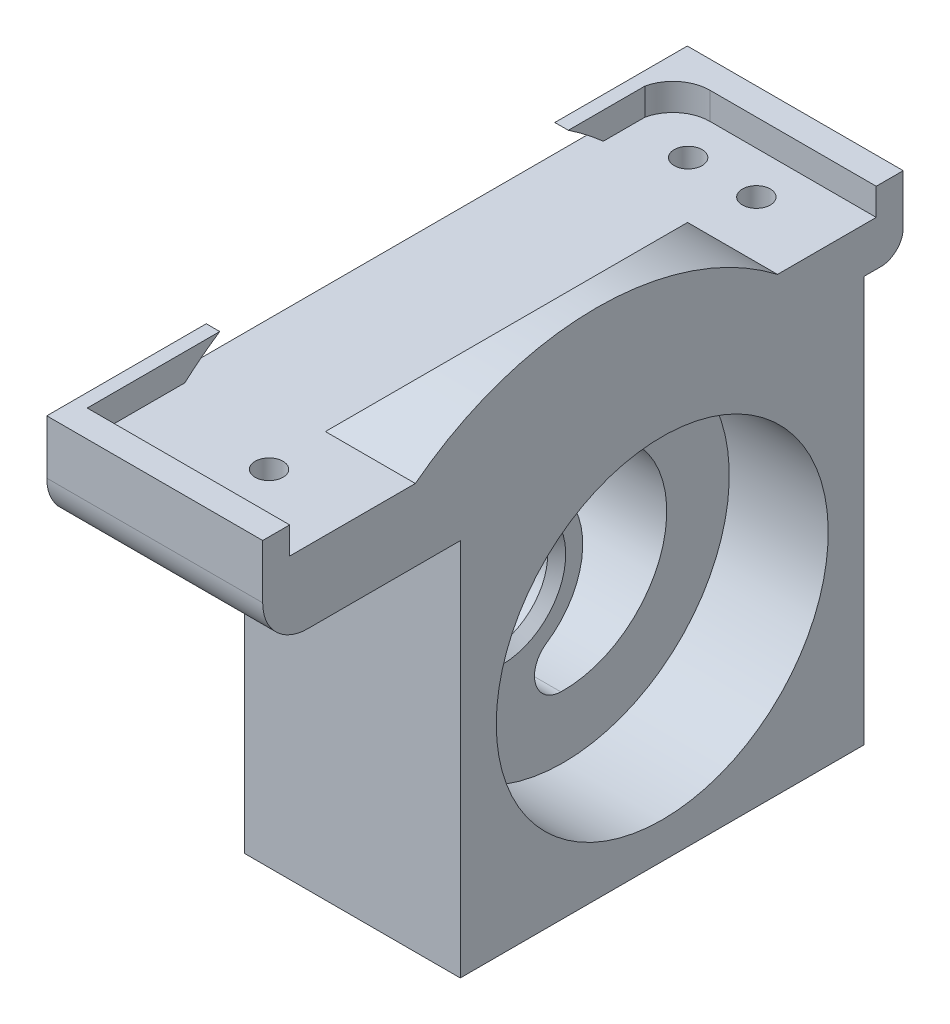
SolidWorks part; units mm, degrees
note: The reader was unsure of these and kept them because the rebuilt part matched: shared geometry of "Sketch1<3>", "Sketch1<4>", "Sketch3<3>", "Sketch3<4>", "Sketch3<5>".
ref_plane "Front Plane" through (0, 0, 0) normal (0, 0, 1) x (1, 0, 0)
ref_plane "Top Plane" through (0, 0, 0) normal (0, 1, 0) x (1, 0, 0)
ref_plane "Right Plane" through (0, 0, 0) normal (1, 0, 0) x (0, 0, -1)
sketch "Sketch1" plane through (-50.6502, 0, 0) normal (-1, 0, 0) x (0, 0, 1)
  line L1 (19.0917, -47.1626) -> (63.9917, -47.1626)
  line L2 (63.9917, -47.1626) -> (63.9917, -5.0626)
  line L3 (63.9917, -5.0626) -> (80.9548, -5.0626)
  line L4 (85.9548, -0.0626) -> (85.9548, 5.9374)
  line L5 (85.9548, 5.9374) -> (82.9548, 5.9374)
  line L6 (82.9548, 5.9374) -> (82.9548, 2.9374)
  line L7 (82.9548, 2.9374) -> (17.7548, 2.9374)
  line L8 (17.7548, 2.9374) -> (17.7548, 5.9374)
  line L9 (17.7548, 5.9374) -> (14.7548, 5.9374)
  line L10 (14.7548, 5.9374) -> (14.7548, 0.4374)
  line L11 (14.7548, 0.4374) -> (14.7548, 5.9374) construction
  line L13 (17.2548, -2.0626) -> (19.0917, -2.0626)
  line L14 (19.0917, -2.0626) -> (19.0917, -47.1626)
  line L15 (19.0917, -2.0626) -> (17.2548, -2.0626) construction
  line L16 (19.0917, -24.7126) -> (19.0917, -2.0626) construction
  line L17 (63.9917, -47.1626) -> (19.0917, -47.1626) construction
  line L18 (63.9917, -24.7126) -> (63.9917, -47.1626) construction
  line L19 (14.7548, 5.9374) -> (17.7548, 5.9374) construction
  line L20 (17.7548, 5.9374) -> (17.7548, 2.9374) construction
  line L21 (17.7548, 2.9374) -> (82.9548, 2.9374) construction
  line L22 (82.9548, 2.9374) -> (82.9548, 5.9374) construction
  line L23 (82.9548, 5.9374) -> (85.9548, 5.9374) construction
  line L24 (85.9548, 5.9374) -> (85.9548, -0.0626) construction
  line L25 (80.9548, -5.0626) -> (63.9917, -5.0626) construction
  circle A0 centre (48.3792, -23.2131) radius 6.11
  circle A1 centre (48.3792, -23.2131) radius 3.075
  circle A2 centre (48.3792, -23.2131) radius 6.11 construction
  circle A3 centre (48.3792, -23.2131) radius 3.075 construction
  circle A4 centre (41.5417, -24.7126) radius 18.45
  circle A5 centre (41.5417, -24.7126) radius 18.45 construction
  circle A6 centre (41.5417, -24.7126) radius 22.45
  circle A7 centre (41.5417, -24.7126) radius 22.45 construction
  arc A8 (80.9548, -5.0626) -> (85.9548, -0.0626) centre (80.9548, -0.0626) ccw
  arc A9 (14.7548, 0.4374) -> (17.2548, -2.0626) centre (17.2548, 0.4374) ccw
  arc A10 (14.7548, 0.4374) -> (17.2548, -2.0626) centre (17.2548, 0.4374) ccw construction
  arc A11 (80.9548, -5.0626) -> (85.9548, -0.0626) centre (80.9548, -0.0626) ccw construction
  circle M20 centre (48.3792, -23.2131) radius 5.25
extrude "Boss-Extrude1" add sketch "Sketch1" along normal up to surface (5.5 mm away) contours A1 M20 | A0 M20 | A4 A0 | A6 A4 | A6 L14 L1 | A6 L1 L2 | L10 A9 L13 L14 A6 L2 L3 A8 L4 L5 L6 L7 L8 L9
extrude "Boss-Extrude2" add sketch "Sketch1<3>" against normal up to surface (6 mm away) contours A4 A0 | A6 A4 | A6 L14 L1 | A6 L1 L2 | L10 A9 L13 L14 A6 L2 L3 A8 L4 L5 L6 L7 L8 L9
sketch "Sketch1<3>" plane through (-50.6502, 0, 0) normal (-1, 0, 0) x (0, 0, 1) same geometry as "Sketch1"
extrude "Boss-Extrude3" add sketch "Sketch1<4>" against normal up to surface (11 mm away) from surface at -6 contours A6 L14 L1 | A6 L1 L2 | A6 A4 | L10 A9 L13 L14 A6 L2 L3 A8 L4 L5 L6 L7 L8 L9 starting at face at (-44.6502, -5.7236, 47.6952)
sketch "Sketch1<4>" plane through (-50.6502, 0, 0) normal (-1, 0, 0) x (0, 0, 1) same geometry as "Sketch1"
sketch "Sketch2" plane through (-33.6502, 0, 0) normal (1, 0, 0) x (0, 0, -1)
  line L0 (-17.7548, 2.9374) -> (-82.9548, 2.9374) construction
  line L1 (-28.7263, 2.9374) -> (-68.9833, 2.9374)
  arc A0 (-28.7263, 2.9374) -> (-68.9833, 2.9374) centre (-48.8548, -23.2131) ccw
  arc A1 (-28.7263, 2.9374) -> (-68.9833, 2.9374) centre (-48.8548, -23.2131) ccw construction
  line M7 (-17.7548, 2.9374) -> (-82.9548, 2.9374)
extrude "Boss-Extrude4" add sketch "Sketch2" against normal blind 10 contours A0 M7
draft "Draft1" type of draft neutral plane draft angle 45 faces to draft 1 face at (-43.6502, 6.3621, 48.8548) neutral plane through (-144.9705, 2.9374, 0) neutral plane normal (0, 1, 0) parameters "D1"=45
sketch "Sketch3" plane through (0, 2.9374, 0) normal (0, 1, 0) x (1, 0, 0)
  line L0 (-56.1502, -17.7548) -> (-33.6502, -17.7548) construction
  line L1 (-56.1502, -82.9548) -> (-56.1502, -17.7548) construction
  line L2 (-56.1502, -17.7548) -> (-33.6502, -17.7548) construction
  line L3 (85.3271, -19.0917) -> (85.3271, -24.1003) construction
  line L4 (-42.2775, -25.7457) -> (-39.4275, -24.1003)
  line L5 (-39.4275, -24.1003) -> (-39.4275, -20.8094)
  line L6 (-39.4275, -20.8094) -> (-42.2775, -19.1639)
  line L7 (-42.2775, -19.1639) -> (-45.1275, -20.8094)
  line L8 (-45.1275, -20.8094) -> (-45.1275, -24.1003)
  line L9 (-45.1275, -24.1003) -> (-42.2775, -25.7457)
  line L10 (-49.8593, -25.7457) -> (-47.0093, -24.1003)
  line L11 (-47.0093, -24.1003) -> (-47.0093, -20.8094)
  line L12 (-47.0093, -20.8094) -> (-49.8593, -19.1639)
  line L13 (-49.8593, -19.1639) -> (-52.7093, -20.8094)
  line L14 (-52.7093, -20.8094) -> (-52.7093, -24.1003)
  line L15 (-52.7093, -24.1003) -> (-49.8593, -25.7457)
  line L16 (-39.8593, -75.7484) -> (-41.5048, -72.8984)
  line L17 (-41.5048, -72.8984) -> (-44.7957, -72.8984)
  line L18 (-44.7957, -72.8984) -> (-46.4411, -75.7484)
  line L19 (-46.4411, -75.7484) -> (-44.7957, -78.5984)
  line L20 (-44.7957, -78.5984) -> (-41.5048, -78.5984)
  line L21 (-41.5048, -78.5984) -> (-39.8593, -75.7484)
  line L23 (90.6952, -72.8984) -> (87.4043, -72.8984) construction
  line L24 (85.3271, -24.1003) -> (88.1771, -25.7457) construction
  line L25 (-52.7093, -20.8094) -> (-52.7093, -19.0917)
  line L26 (-52.7093, -19.0917) -> (-47.0093, -19.0917)
  line L27 (-47.0093, -19.0917) -> (-47.0093, -20.8094)
  line L28 (-45.1275, -20.8094) -> (-45.1275, -19.0917)
  line L29 (-45.1275, -19.0917) -> (-39.4275, -19.0917)
  line L30 (-39.4275, -19.0917) -> (-39.4275, -20.8094)
  line L31 (-56.1502, -19.0917) -> (-33.6502, -19.0917) construction
  arc A0 (-52.1502, -17.7548) -> (-56.1502, -20.9548) centre (-52.1502, -21.8548) ccw
  arc A1 (-52.1502, -17.8548) -> (-56.1502, -21.8548) centre (-52.1502, -21.8548) ccw construction
  circle A2 centre (-49.8593, -22.4548) radius 1.55
  circle A3 centre (-42.2775, -22.4548) radius 1.55
  circle A4 centre (-49.8593, -22.4548) radius 1.55 construction
  circle A5 centre (-42.2775, -22.4548) radius 1.55 construction
  circle A6 centre (-43.1502, -75.7484) radius 1.55
  circle A7 centre (-43.1502, -75.7484) radius 1.55 construction
  circle A8 centre (-42.2775, -22.4548) radius 2.85 construction
  circle A9 centre (-49.8593, -22.4548) radius 2.85 construction
  circle A10 centre (-43.1502, -75.7484) radius 2.85 construction
  line M15 (-33.6502, -17.7548) -> (-56.1502, -17.7548)
  line M16 (-56.1502, -17.7548) -> (-56.1502, -82.9548)
extrude "Boss-Extrude5" add sketch "Sketch3" along normal up to surface (3 mm away) contours A0 M15 M16 up to face at (-44.9002, 5.9374, 16.2548)
sketch "Sketch4" plane through (-56.1502, 0, 0) normal (-1, 0, 0) x (0, 0, 1)
  line L0 (20.9548, 5.9374) -> (29.4834, 5.9374)
  line L1 (82.9548, 5.9374) -> (68.2262, 5.9374)
  line L12 (82.9548, 2.9374) -> (20.9548, 2.9374)
  line L13 (20.9548, 2.9374) -> (20.9548, 5.9374)
  line L14 (20.9548, 5.9374) -> (14.7548, 5.9374)
  line L15 (14.7548, 5.9374) -> (14.7548, 0.4374)
  line L16 (17.2548, -2.0626) -> (19.0917, -2.0626)
  line L17 (19.0917, -2.0626) -> (19.0917, -47.1626)
  line L18 (19.0917, -47.1626) -> (63.9917, -47.1626)
  line L19 (63.9917, -47.1626) -> (63.9917, -5.0626)
  line L20 (63.9917, -5.0626) -> (80.9548, -5.0626)
  line L21 (85.9548, -0.0626) -> (85.9548, 5.9374)
  line L22 (85.9548, 5.9374) -> (82.9548, 5.9374)
  line L23 (82.9548, 5.9374) -> (82.9548, 2.9374)
  line L24 (82.9548, 2.9374) -> (20.9548, 2.9374)
  line L25 (20.9548, 2.9374) -> (20.9548, 5.9374)
  line L26 (20.9548, 5.9374) -> (14.7548, 5.9374)
  line L27 (14.7548, 5.9374) -> (14.7548, 0.4374)
  line L28 (17.2548, -2.0626) -> (19.0917, -2.0626)
  line L29 (19.0917, -2.0626) -> (19.0917, -47.1626)
  line L30 (19.0917, -47.1626) -> (63.9917, -47.1626)
  line L31 (63.9917, -47.1626) -> (63.9917, -5.0626)
  line L32 (63.9917, -5.0626) -> (80.9548, -5.0626)
  line L33 (85.9548, -0.0626) -> (85.9548, 5.9374)
  line L34 (85.9548, 5.9374) -> (82.9548, 5.9374)
  line L35 (82.9548, 5.9374) -> (82.9548, 2.9374)
  arc A0 (72.1175, 2.9374) -> (25.5921, 2.9374) centre (48.8548, -23.2131) ccw construction
  arc A1 (25.5921, 2.9374) -> (29.4834, 5.9374) centre (48.8548, -23.2131) cw
  arc A2 (14.7548, 0.4374) -> (17.2548, -2.0626) centre (17.2548, 0.4374) ccw
  arc A3 (80.9548, -5.0626) -> (85.9548, -0.0626) centre (80.9548, -0.0626) ccw
  arc A4 (14.7548, 0.4374) -> (17.2548, -2.0626) centre (17.2548, 0.4374) ccw
  arc A5 (80.9548, -5.0626) -> (85.9548, -0.0626) centre (80.9548, -0.0626) ccw
  arc A6 (72.1175, 2.9374) -> (68.2262, 5.9374) centre (48.8548, -23.2131) ccw
  line M15 (82.9548, 2.9374) -> (20.9548, 2.9374)
  line M16 (20.9548, 2.9374) -> (20.9548, 5.9374)
  line M17 (20.9548, 5.9374) -> (14.7548, 5.9374)
  line M18 (14.7548, 5.9374) -> (14.7548, 0.4374)
  arc M19 (14.7548, 0.4374) -> (17.2548, -2.0626) centre (17.2548, 0.4374) ccw
  line M20 (17.2548, -2.0626) -> (19.0917, -2.0626)
  line M21 (19.0917, -2.0626) -> (19.0917, -47.1626)
  line M22 (19.0917, -47.1626) -> (63.9917, -47.1626)
  line M23 (63.9917, -47.1626) -> (63.9917, -5.0626)
  line M24 (63.9917, -5.0626) -> (80.9548, -5.0626)
  arc M25 (80.9548, -5.0626) -> (85.9548, -0.0626) centre (80.9548, -0.0626) ccw
  line M26 (85.9548, -0.0626) -> (85.9548, 5.9374)
  line M27 (85.9548, 5.9374) -> (82.9548, 5.9374)
  line M28 (82.9548, 5.9374) -> (82.9548, 2.9374)
  circle M29 centre (48.3792, -23.2131) radius 3.075
  dimension "D1" = 0
extrude "Boss-Extrude6" add sketch "Sketch4" along normal blind 1.5 contours L24 M28 M15 M16 M17 M18 M19 M20 M21 M22 M23 M24 M25 M26 M27 M29 | L24 A1 L0 M16 | A6 L1 M15 M28
extrude "Cut-Extrude1" cut sketch "Sketch3<3>" against normal up to surface (11 mm away) contours A2 | A3 | A6
sketch "Sketch3<3>" plane through (0, 2.9374, 0) normal (0, 1, 0) x (1, 0, 0) same geometry as "Sketch3"
extrude "Cut-Extrude2" cut sketch "Sketch3<4>" along normal up to surface (2.6 mm away) from surface contours L8 L9 L4 L5 L6 L7 A3 | L14 L15 L10 L11 L12 L13 A2 | L27 L26 L25 L13 L12 | L30 L29 L28 L7 L6
sketch "Sketch3<4>" plane through (0, 2.9374, 0) normal (0, 1, 0) x (1, 0, 0) same geometry as "Sketch3"
extrude "Cut-Extrude3" cut sketch "Sketch3<5>" along normal up to surface (2.5 mm away) from surface at -8 contours L20 L21 L16 L17 L18 L19 A6 starting at face at (-44.7002, -5.0626, 75.7484)
sketch "Sketch3<5>" plane through (0, 2.9374, 0) normal (0, 1, 0) x (1, 0, 0) same geometry as "Sketch3"
sketch "Sketch5" plane through (-57.6502, 0, 0) normal (-1, 0, 0) x (0, 0, 1)
  arc A0 (40.7201, -18.4867) -> (36.9761, -14.1578) centre (38.1671, -16.9112) ccw construction
  arc A1 (40.7201, -18.4867) -> (43.4011, -30.711) centre (48.3792, -23.2131) ccw construction
  arc A2 (41.8123, -36.2095) -> (43.4011, -30.711) centre (41.7417, -33.2103) ccw construction
  arc A3 (36.9761, -14.1578) -> (41.8123, -36.2095) centre (41.5417, -24.7126) ccw construction
  arc A4 (40.7201, -18.4867) -> (36.9761, -14.1578) centre (38.1671, -16.9112) ccw
  arc A5 (40.7201, -18.4867) -> (43.4011, -30.711) centre (48.3792, -23.2131) ccw
  arc A6 (41.8123, -36.2095) -> (43.4011, -30.711) centre (41.7417, -33.2103) ccw
  arc A7 (36.9761, -14.1578) -> (41.8123, -36.2095) centre (41.5417, -24.7126) ccw
extrude "Cut-Extrude4" cut sketch "Sketch5" against normal up to surface (13 mm away) up to face at (-44.6502, -29.3231, 48.3792)
chamfer "Chamfer1" distance 1 angle 45 1 edges at (-44.6502, -29.3231, 48.3792)
